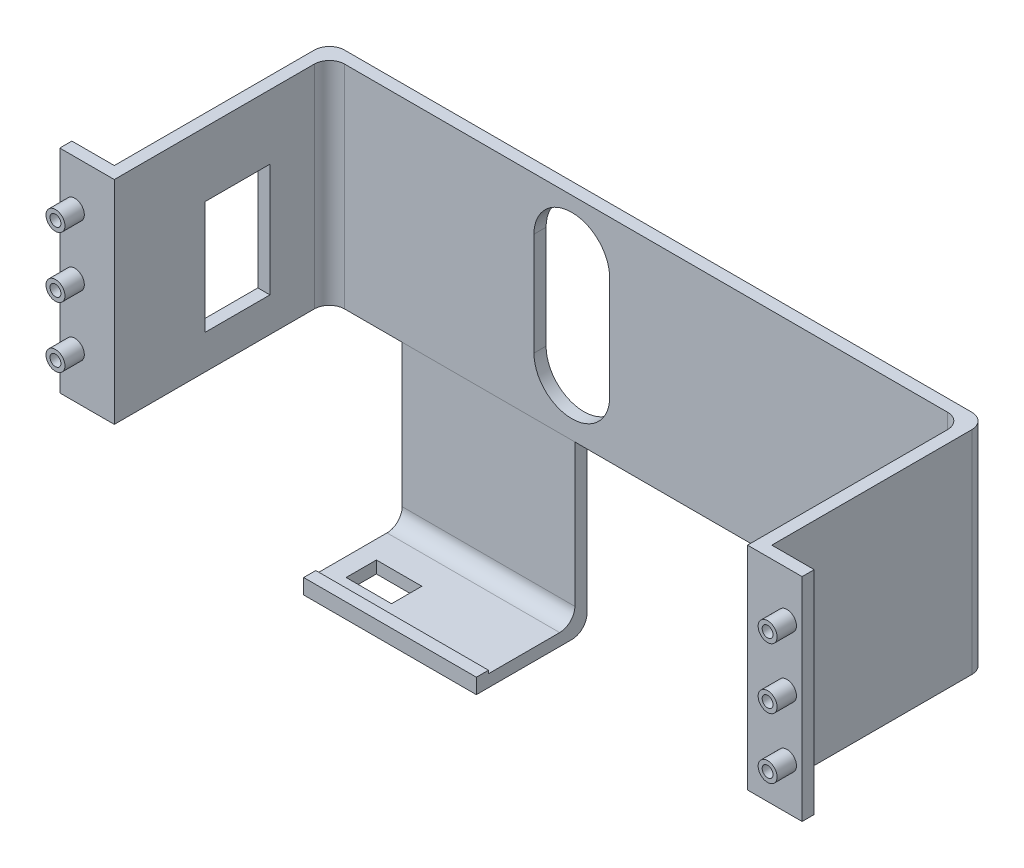
SolidWorks part; units mm, degrees
ref_plane "Front Plane" through (0, 0, 0) normal (0, 0, 1) x (1, 0, 0)
ref_plane "Top Plane" through (0, 0, 0) normal (0, 1, 0) x (1, 0, 0)
ref_plane "Right Plane" through (0, 0, 0) normal (1, 0, 0) x (0, 0, -1)
sketch "Sketch1" plane through (0, 0, 0) normal (0, 1, 0) x (1, 0, 0)
  line L0 (0, 0) -> (18, 0)
  line L1 (18, 0) -> (18, 71)
  line L2 (227, 71) -> (18, 71)
  line L3 (0, 0) -> (0, 4)
  line L4 (0, 4) -> (14, 4)
  line L5 (14, 4) -> (14, 75)
  line L6 (14, 75) -> (231, 75)
  line L7 (122.5, 41.705) -> (122.5, 38.705) construction
  line L8 (231, 4) -> (231, 75)
  line L9 (245, 4) -> (231, 4)
  line L10 (245, 0) -> (245, 4)
  line L11 (227, 0) -> (227, 71)
  line L12 (245, 0) -> (227, 0)
  point P12 (122.5, 75)
  point P16 (122.5, 71)
  dimension "D1" = 4
  dimension "D2" = 4
  dimension "D3" = 4
  dimension "D4" = 18
  dimension "D5" = 122.5
  dimension "D6" = 75
extrude "Boss-Extrude1" add sketch "Sketch1" along normal blind 70
sketch "Sketch2" plane through (0, 0, -4) normal (0, 0, -1) x (-1, 0, 0)
  line L0 (-245, 70) -> (-231, 70) construction
  line L1 (-122.5, 70) -> (-122.5, 0) construction
  line L2 (-231, 70) -> (-14, 70) construction
  line L3 (-231, 0) -> (-14, 0) construction
  circle A0 centre (-240.02, 55) radius 1.8
  circle A1 centre (-240.02, 35) radius 1.8
  circle A2 centre (-240.02, 15) radius 1.8
  circle A3 centre (-4.98, 15) radius 1.8
  circle A4 centre (-4.98, 35) radius 1.8
  circle A5 centre (-4.98, 55) radius 1.8
  dimension "D1" = 20
  dimension "D2" = 20
  dimension "D3" = 15
  dimension "D4" = 117.52
extrude "Cut-Extrude1" cut sketch "Sketch2" against normal through all
sketch "Sketch3" plane through (0, 0, -71) normal (0, 0, 1) x (1, 0, 0)
  line L0 (98, 52.6161) -> (98, 18.6333) construction
  line L1 (110.5, 52.6161) -> (110.5, 18.6333)
  line L2 (85.5, 52.6161) -> (85.5, 18.6333)
  line L3 (18, 70) -> (18, 0) construction
  arc A0 (110.5, 52.6161) -> (85.5, 52.6161) centre (98, 52.6161) ccw
  arc A1 (85.5, 18.6333) -> (110.5, 18.6333) centre (98, 18.6333) ccw
  point P2 (98, 35.6247)
  dimension "D1" = 80
extrude "Cut-Extrude2" cut sketch "Sketch3" against normal up to next
sketch "Sketch4" plane through (0, 0, -75) normal (0, 0, -1) x (-1, 0, 0)
  line L0 (-231, 0) -> (-14, 0) construction
  line L1 (-99, 0) -> (-42, 0)
  line L2 (-99, 0) -> (-99, -56)
  line L3 (-99, -56) -> (-42, -56)
  line L4 (-42, 0) -> (-42, -56)
  line L5 (-14, 70) -> (-14, 0) construction
  dimension "D1" = 56
  dimension "D2" = 57
  dimension "D3" = 28
extrude "Boss-Extrude2" add sketch "Sketch4" against normal blind 36.5 separate body
sketch "Sketch5" plane through (99, 0, 0) normal (1, 0, 0) x (0, 0, -1)
  line L0 (4, 0) -> (75, 0) construction
  line L1 (38.5, 0) -> (71, 0)
  line L2 (38.5, 0) -> (38.5, -51)
  line L3 (42.5, -52) -> (71, -52)
  line L4 (71, 0) -> (71, -52)
  line L5 (38.5, 0) -> (38.5, -56) construction
  line L6 (75, 0) -> (75, -56) construction
  line L7 (38.5, -56) -> (75, -56) construction
  line L11 (38.5, -51) -> (42.5, -51)
  line L12 (42.5, -52) -> (42.5, -51)
  dimension "D1" = 4
  dimension "D2" = 4
  dimension "D3" = 4
  dimension "D4" = 1
extrude "Cut-Extrude3" cut sketch "Sketch5" against normal through all
fillet "Fillet1" radius 5 4 edges at (227, 35, -71) (18, 35, -71) (14, 35, -75) (231, 35, -75)
fillet "Fillet2" radius 5 2 edges at (70.5, -56, -75) (70.5, -52, -71)
sketch "Sketch6" plane through (0, -56, 0) normal (0, -1, 0) x (1, 0, 0)
  line L0 (42, -38.5) -> (42, -70) construction
  line L1 (48, -46.5) -> (63, -46.5)
  line L2 (48, -46.5) -> (48, -56.5)
  line L3 (48, -56.5) -> (63, -56.5)
  line L4 (63, -46.5) -> (63, -56.5)
  line L5 (99, -38.5) -> (42, -38.5) construction
  dimension "D1" = 15
  dimension "D2" = 10
  dimension "D3" = 6
  dimension "D4" = 8
extrude "Cut-Extrude4" cut sketch "Sketch6" against normal through all
sketch "Sketch7" plane through (0, 0, 0) normal (0, 0, 1) x (1, 0, 0)
  line L0 (122.5, 70) -> (122.5, 0) construction
  line L1 (23, 70) -> (222, 70) construction
  line L2 (23, 0) -> (222, 0) construction
  circle A0 centre (4.98, 55) radius 3.125
  circle A1 centre (4.98, 35) radius 3.125
  circle A2 centre (4.98, 15) radius 3.125
  circle A3 centre (4.98, 55) radius 1.8
  circle A4 centre (4.98, 35) radius 1.8
  circle A5 centre (4.98, 15) radius 1.8
  circle A6 centre (240.02, 15) radius 1.8
  circle A7 centre (240.02, 35) radius 1.8
  circle A8 centre (240.02, 55) radius 1.8
  circle A9 centre (240.02, 15) radius 3.125
  circle A10 centre (240.02, 35) radius 3.125
  circle A11 centre (240.02, 55) radius 3.125
extrude "Boss-Extrude4" add sketch "Sketch7" along normal blind 6.4
sketch "Sketch8" plane through (14, 0, 0) normal (-1, 0, 0) x (0, 0, 1)
  line L0 (-4, 70) -> (-4, 0) construction
  line L1 (-51.3632, 48.7055) -> (-30, 48.7055)
  line L2 (-51.3632, 48.7055) -> (-51.3632, 11.3431)
  line L3 (-51.3632, 11.3431) -> (-30, 11.3431)
  line L4 (-30, 48.7055) -> (-30, 11.3431)
  dimension "D1" = 26
extrude "Cut-Extrude5" cut sketch "Sketch8" against normal up to next
